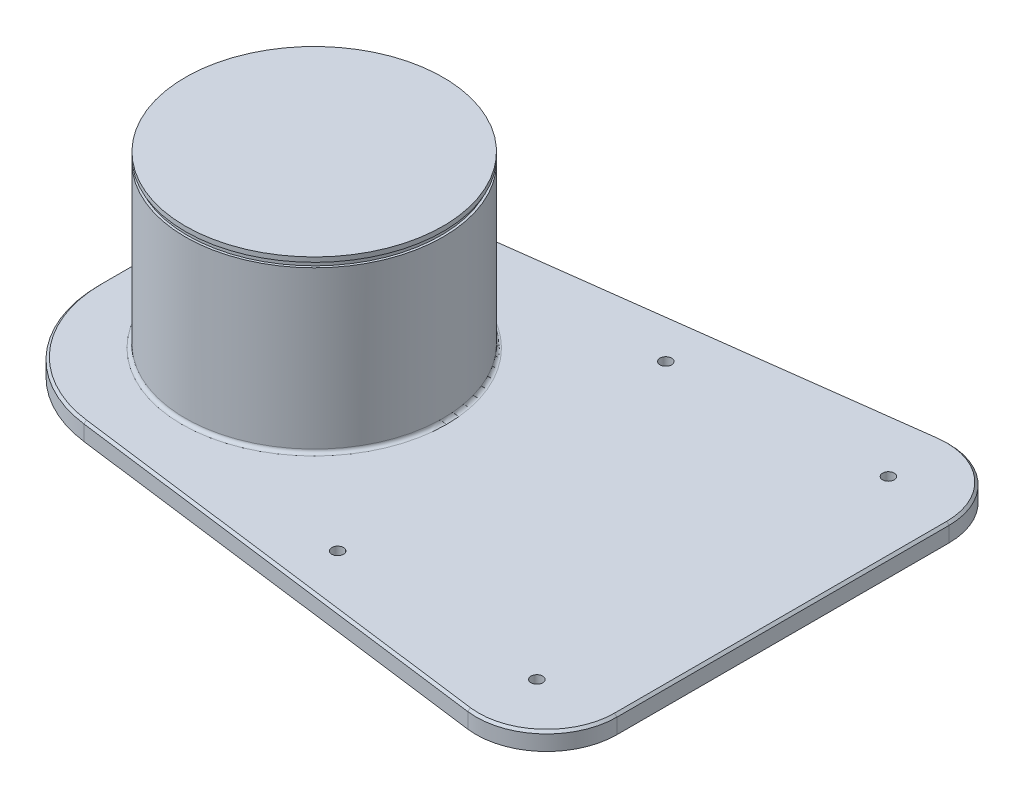
SolidWorks part; units mm, degrees
material "Acier non allié"
ref_plane "Plan de face" through (0, 0, 0) normal (0, 0, 1) x (1, 0, 0)
ref_plane "Plan de dessus" through (0, 0, 0) normal (0, 1, 0) x (1, 0, 0)
ref_plane "Plan de droite" through (0, 0, 0) normal (1, 0, 0) x (0, 0, -1)
sketch "Esquisse1" plane through (0, 0, 0) normal (0, 1, 0) x (1, 0, 0)
  line L0 (-140, 0) -> (400, 0) construction
  line L1 (-140, 43.3389) -> (-140, -43.3389)
  line L2 (-44.1409, -152.4262) -> (332.2868, -201.2224)
  line L3 (400, -141.7202) -> (400, 141.7202)
  line L4 (332.2868, 201.2224) -> (-44.1409, 152.4262)
  arc A0 (-140, 43.3389) -> (-44.1409, 152.4262) centre (-30, 43.3389) cw
  arc A1 (-140, -43.3389) -> (-44.1409, -152.4262) centre (-30, -43.3389) ccw
  arc A2 (332.2868, -201.2224) -> (400, -141.7202) centre (340, -141.7202) ccw
  arc A3 (400, 141.7202) -> (332.2868, 201.2224) centre (340, 141.7202) ccw
  point P9 (-140, 140)
  point P12 (-140, -140)
  point P15 (400, -210)
  point P18 (400, 210)
  dimension "D5" = 110
  dimension "D6" = 110
  dimension "D7" = 60
  dimension "D8" = 60
  dimension "D1" = 140
  dimension "D2" = 400
  dimension "D3" = 280
  dimension "D4" = 420
extrude "Boss.-Extru.1" add sketch "Esquisse1" along normal blind 15
sketch "Esquisse2" plane through (0, 15, 0) normal (0, 1, 0) x (1, 0, 0)
  circle A0 centre (0, 0) radius 110
  dimension "D1" = 220
extrude "Boss.-Extru.2" add sketch "Esquisse2" along normal blind 145
ref_plane "Groove_Plane" through (0, 156, 0) normal (0, 1, 0) x (1, 0, 0)
sketch "Esquisse3" plane through (0, 156, 0) normal (0, 1, 0) x (1, 0, 0)
  circle A0 centre (0, 0) radius 111
  circle A1 centre (0, 0) radius 108
  dimension "D1" = 222
  dimension "D2" = 216
extrude "Enlèv. mat.-Extru.1" cut sketch "Esquisse3" against normal blind 4
sketch "Esquisse4" plane through (0, 15, 0) normal (0, 1, 0) x (1, 0, 0)
  line L0 (0, 0) -> (340, 0) construction
  circle A0 centre (340, -150) radius 5
  circle A1 centre (340, 150) radius 5
  circle A2 centre (160, -140) radius 5
  circle A3 centre (160, 140) radius 5
  dimension "D1" = 10
  dimension "D2" = 371.6181
  dimension "D3" = 212.6029
  dimension "D4" = 300
  dimension "D5" = 280
extrude "Enlèv. mat.-Extru.2" cut sketch "Esquisse4" against normal through all
fillet "Congé1" radius 3 1 edges at (0, 15, 110)
chamfer "Chanfrein1" distance 2 angle 45 8 edges at (379.6056, 15, 186.7912) (400, 15, 0) (144.0729, 15, 176.8243) (379.6056, 15, -186.7912) (-112.6302, 15, 115.9491) (144.0729, 15, -176.8243) (-140, 15, 0) (-112.6302, 15, -115.9491)
ref_axis "Axis_J1" through (0, 152, 0) along (0, -1, 0)
